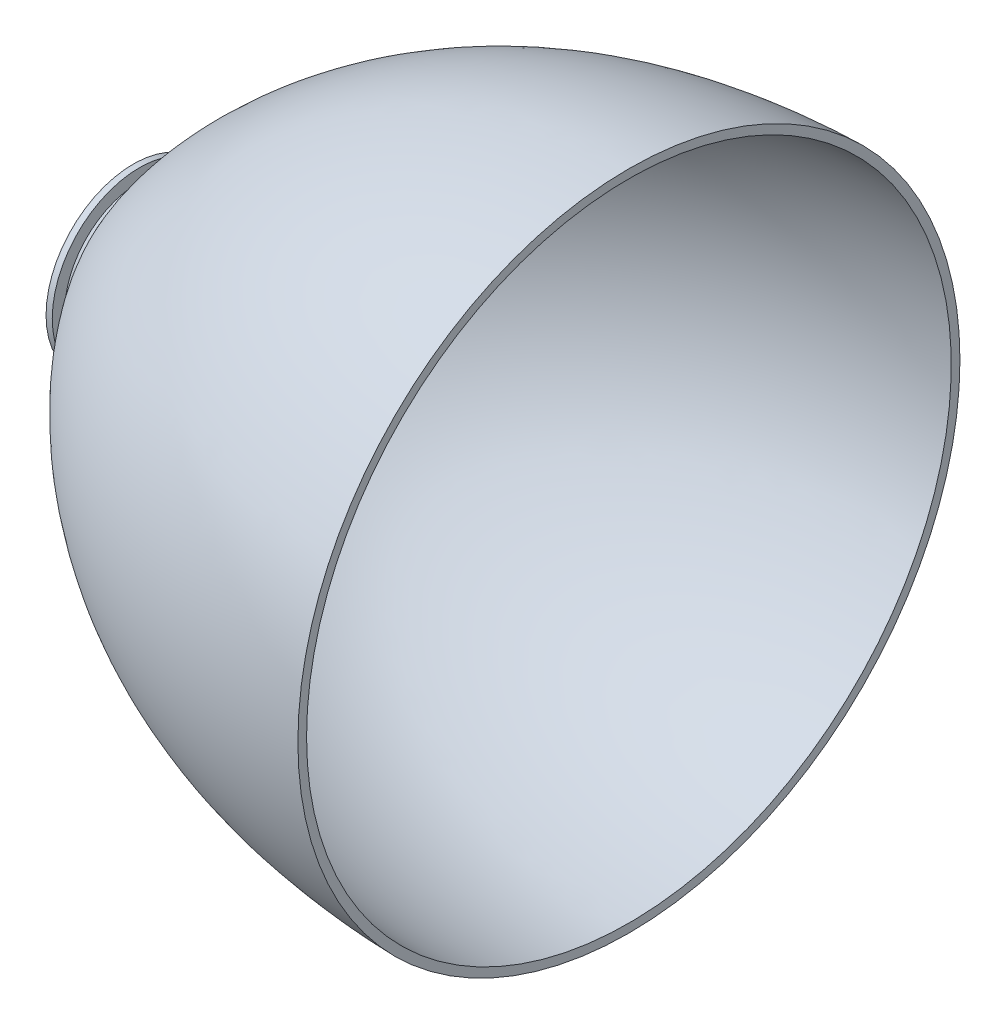
SolidWorks part; units mm, degrees
material "A286 Iron Base Superalloy"
ref_plane "Front Plane" through (0, 0, 0) normal (0, 0, 1) x (1, 0, 0)
ref_plane "Top Plane" through (0, 0, 0) normal (0, 1, 0) x (1, 0, 0)
ref_plane "Right Plane" through (0, 0, 0) normal (1, 0, 0) x (0, 0, -1)
sketch "Sketch1" plane through (0, 0, 0) normal (0, 0, 1) x (1, 0, 0)
  line L0 (-1229.8282, 0) -> (1426.3964, 0) construction
  line L1 (0, -63.5) -> (0, 63.5) construction
  line L2 (0, 0) -> (500, 0) construction
  line L3 (500, -330.2) -> (500, 330.2) construction
  line L5 (500, 339.09) -> (500, 330.2)
  line L6 (0, -72.39) -> (0, -63.5)
  line L7 (500, -339.09) -> (500, -330.2)
  line L8 (-412.8242, -144.8099) -> (-412.8242, 144.8099) construction
  line L9 (-412.8242, 144.8099) -> (-412.8242, 153.6999)
  line L10 (-412.8242, -144.8099) -> (-412.8242, -153.6999)
  spline S0 degree 2 poles (0, 63.5) (163.7773, 321.6338) (500, 330.2) knots 0 0 0 1 1 1
  spline S1 degree 2 poles (0, -63.5) (163.7773, -321.6338) (500, -330.2) knots 0 0 0 1 1 1
  spline S2 degree 2 poles (0, -72.39) (163.7773, -330.5238) (500, -339.09) knots 0 0 0 1 1 1
  spline S3 degree 2 poles (0, -63.5) (163.7773, -321.6338) (500, -330.2) knots 0 0 0 1 1 1
  spline S4 degree 2 poles (0, 72.39) (163.7773, 330.5238) (500, 339.09) knots 0 0 0 1 1 1
  spline S5 degree 2 poles (0, 63.5) (-192.2835, 162.6782) (-412.8242, 144.8099) knots 0 0 0 1 1 1
  spline S6 degree 2 poles (0, -63.5) (-192.2835, -162.6782) (-412.8242, -144.8099) knots 0 0 0 1 1 1
  spline S7 degree 2 poles (0, -72.39) (-189.3535, -181.7828) (-412.8242, -153.6999) knots 0 0 0 1 1 1
  spline S9 degree 2 poles (0, 72.39) (-189.3535, 181.7828) (-412.8242, 153.6999) knots 0 0 0 1 1 1
  point P8 (0, 0)
  point P14 (500, 0)
  point P22 (-412.8242, 0)
  dimension "D4" = 8.89
  dimension "D1" = 127
  dimension "D2" = 500
  dimension "D3" = 660.4
  dimension "D5" = 8.89
  dimension "D6" = 8.89
  dimension "D7" = 289.6197
revolve "Revolve3" add sketch "Sketch1" angle 360 about L0 region at (490.4648, 334.645, 0)
ref_plane "Plane1" through (0, 0, 0) normal (1, 0, 0) x (0, 0, -1)
ref_plane "Plane2" through (-7.62, 0, 0) normal (-1, 0, 0) x (0, 0, 1)
sketch "Sketch4" plane through (-7.62, 0, 0) normal (-1, 0, 0) x (0, 0, 1)
  line L1 (-1213.2286, 638.9142) -> (1085.9115, 638.9142)
  line L2 (-1213.2286, 638.9142) -> (-1213.2286, -445.9528)
  line L3 (-1213.2286, -445.9528) -> (1085.9115, -445.9528)
  line L4 (1085.9115, 638.9142) -> (1085.9115, -445.9528)
extrude "Cut-Extrude1" cut sketch "Sketch4" along normal blind 554.228
sketch "Sketch5" plane through (-7.62, 0, 0) normal (-1, 0, 0) x (0, 0, 1)
  circle A0 centre (0, 0) radius 89.4288
  circle A1 centre (0, 0) radius 76.7288 construction
  circle A2 centre (0, 0) radius 76.7288
  dimension "D1" = 12.7
extrude "Boss-Extrude1" add sketch "Sketch5" against normal blind 6.35 separate body
